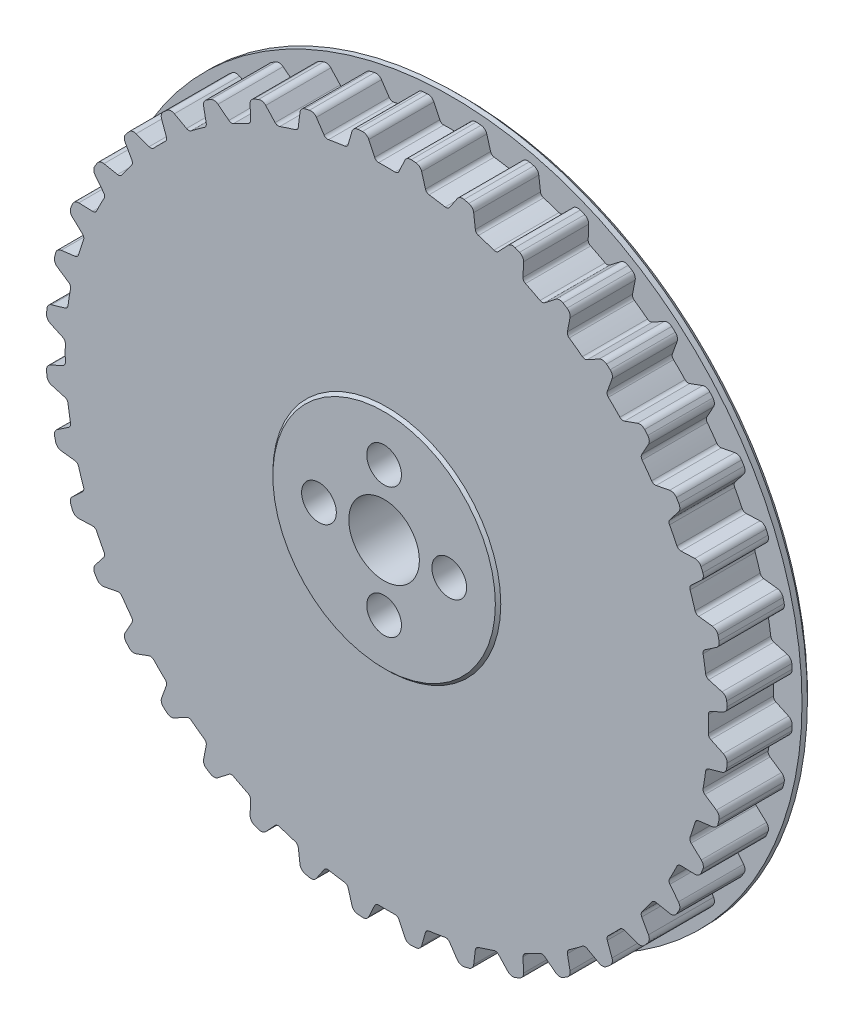
SolidWorks part; units mm, degrees
material "ABS"
ref_plane "正面" through (0, 0, 0) normal (0, 0, 1) x (1, 0, 0)
ref_plane "平面" through (0, 0, 0) normal (0, 1, 0) x (1, 0, 0)
ref_plane "右側面" through (0, 0, 0) normal (1, 0, 0) x (0, 0, -1)
sketch "ｽｹｯﾁ1" plane through (0, 0, 0) normal (0, 0, 1) x (1, 0, 0)
  line L0 (0, 2.608) -> (0, -1.4358) construction
  line L1 (-1.1226, 29.8463) -> (-1.6605, 30.9997)
  line L2 (1.1226, 29.8463) -> (1.6605, 30.9997)
  line L3 (-2.4656, 31.3281) -> (0, 0) construction
  line L4 (0, 0) -> (2.4656, 31.3281) construction
  line L5 (-2.4656, 31.3281) -> (-0.3923, 4.9846)
  line L6 (0.3923, 4.9846) -> (2.4656, 31.3281)
  arc A0 (0.75, 29.6155) -> (-0.75, 29.6155) centre (0, 0) ccw
  arc A1 (-0.75, 29.6155) -> (-1.1226, 29.8463) centre (-0.7601, 30.0154) cw
  arc A2 (-1.6605, 30.9997) -> (-2.2471, 31.3446) centre (-2.2042, 30.7461) ccw
  arc A3 (-2.2471, 31.3446) -> (-2.4656, 31.3281) centre (0, 0) ccw
  arc A4 (2.2471, 31.3446) -> (2.4656, 31.3281) centre (0, 0) cw
  arc A5 (1.6605, 30.9997) -> (2.2471, 31.3446) centre (2.2042, 30.7461) cw
  arc A6 (0.75, 29.6155) -> (1.1226, 29.8463) centre (0.7601, 30.0154) ccw
  arc A7 (-0.3923, 4.9846) -> (0.3923, 4.9846) centre (0, 0) ccw
  dimension "D1" = 1.8
  dimension "D2" = 0.4
  dimension "D3" = 0.6
  dimension "D4" = 31.425
  dimension "D8" = 5
  dimension "D5" = 25
  dimension "D6" = 1.5
  dimension "D7" = 9
extrude "ﾎﾞｽ - 押し出し1" add sketch "ｽｹｯﾁ1" along normal blind 6
pattern_circular "円形ﾊﾟﾀｰﾝ1" count 40 over 360 about axis through (0, 0, 6) along (0, 0, -1) of "ﾎﾞｽ - 押し出し1" reverse direction yes
sketch "ｽｹｯﾁ2" plane through (0, 0, 6) normal (0, 0, 1) x (1, 0, 0)
  line L0 (0, 0) -> (0, 6) construction
  line L1 (0, 0) -> (6, 0) construction
  line L2 (0, 0) -> (0, -6) construction
  line L3 (0, 0) -> (-6, 0) construction
  circle A0 centre (0, 0) radius 3.25
  circle A1 centre (0, 6) radius 1.6
  circle A2 centre (6, 0) radius 1.6
  circle A3 centre (0, -6) radius 1.6
  circle A4 centre (-6, 0) radius 1.6
  point P17 (0, 0)
  dimension "D1" = 6.5
  dimension "D3" = 3.2
  dimension "D2" = 6
  dimension "D4" = 4
sketch "ｽｹｯﾁ4" plane through (0, 0, 0) normal (0, 0, -1) x (-1, 0, 0)
  circle A0 centre (0, 0) radius 32.25
  dimension "D1" = 64.5
extrude "ﾎﾞｽ - 押し出し3" add sketch "ｽｹｯﾁ4" along normal blind 1
extrude "ｶｯﾄ - 押し出し2" cut sketch "ｽｹｯﾁ2" against normal through all
chamfer "面取り1" distance 2 angle 45 4 edges at (1.6, -6, -1) (-4.4, 0, -1) (7.6, 0, -1) (1.6, 6, -1)
sketch "ｽｹｯﾁ5" plane through (0, 0, 6) normal (0, 0, 1) x (1, 0, 0)
  circle A0 centre (0, 0) radius 10
  circle A1 centre (-6, 0) radius 1.6 construction
  circle A2 centre (0, 6) radius 1.6 construction
  circle A3 centre (0, -6) radius 1.6 construction
  circle A4 centre (0, 0) radius 3.25 construction
  circle A5 centre (6, 0) radius 1.6 construction
  circle A6 centre (0, 0) radius 3.25
  circle A7 centre (6, 0) radius 1.6
  circle A8 centre (0, -6) radius 1.6
  circle A9 centre (0, 6) radius 1.6
  circle A10 centre (-6, 0) radius 1.6
  dimension "D1" = 20
extrude "ﾎﾞｽ - 押し出し4" add sketch "ｽｹｯﾁ5" along normal blind 0.25
chamfer "面取り3" distance 0.5 1 edges at (10, 0, 6)
chamfer "面取り4" distance 0.5 angle 45 1 edges at (-32.25, 0, -1)
